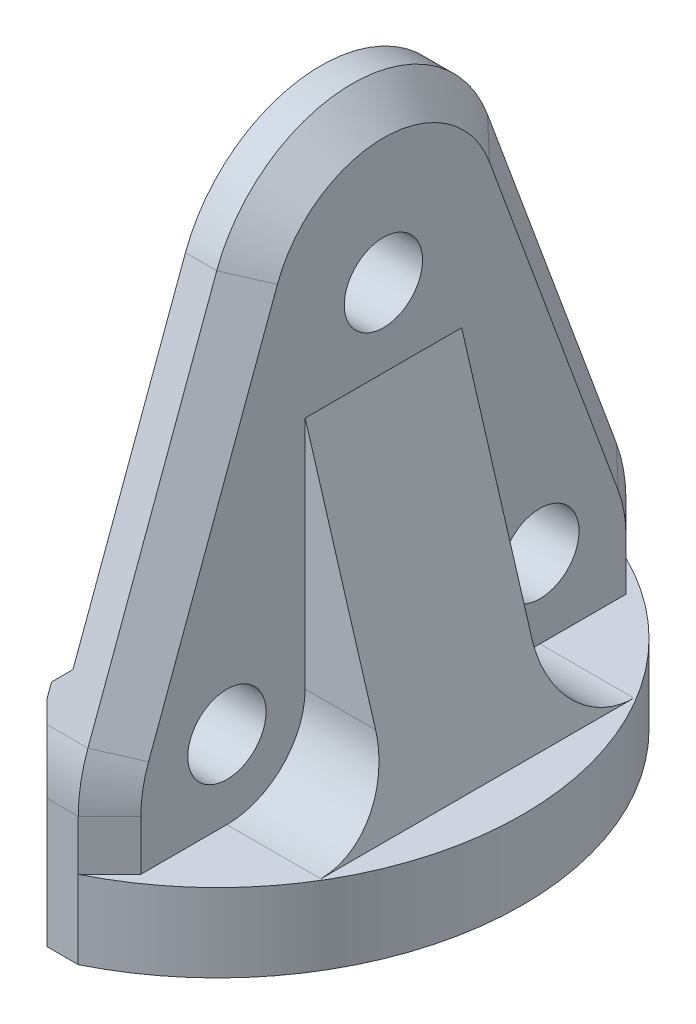
SolidWorks part; units mm, degrees
ref_plane "Front Plane" through (0, 0, 0) normal (0, 0, 1) x (1, 0, 0)
ref_plane "Top Plane" through (0, 0, 0) normal (0, 1, 0) x (1, 0, 0)
ref_plane "Right Plane" through (0, 0, 0) normal (1, 0, 0) x (0, 0, -1)
sketch "Sketch1" plane through (0, 0, 0) normal (1, 0, 0) x (0, 0, -1)
  line L0 (0, 0) -> (35, 0)
  line L1 (35, 0) -> (35, 8.213)
  line L2 (0, 0) -> (0, 8.21)
  line L3 (17.5, 1.5956) -> (17.5, 1.5986) construction
  line L4 (26.1505, 33.9741) -> (34.3813, 11.6759)
  line L5 (8.8494, 33.9737) -> (0.6186, 11.6724)
  arc A0 (0.6186, 11.6724) -> (0, 8.21) centre (10, 8.21) ccw
  arc A1 (17.5, 1.5986) -> (17.5013, 1.5971) centre (25, 8.213) ccw
  arc A2 (26.1505, 33.9741) -> (8.8494, 33.9737) centre (17.5, 30.781) ccw
  arc A5 (17.5, 1.5956) -> (17.5013, 1.5971) centre (10, 8.21) ccw
  arc A6 (35, 8.213) -> (34.3813, 11.6759) centre (25, 8.213) ccw
  dimension "D1" = 20
  dimension "D2" = 20
  dimension "D6" = 18.442
  dimension "D7" = 30.781
  dimension "D3" = 35
  dimension "D4" = 8.213
  dimension "D5" = 8.21
  dimension "D8" = 69.742
extrude "Boss-Extrude1" add sketch "Sketch1" along normal blind 2 contours L5 A0 L2 L0 L1 A6 L4 A2
sketch "Sketch2" plane through (2, 0, 0) normal (1, 0, 0) x (0, 0, -1)
  line L5 (8.8494, 33.9737) -> (0.6186, 11.6724)
  line L6 (0, 8.21) -> (0, 0)
  line L7 (0, 0) -> (35, 0)
  line L8 (35, 0) -> (35, 8.213)
  line L9 (34.3813, 11.6759) -> (26.1505, 33.9741)
  line L10 (8.8494, 33.9737) -> (0.6186, 11.6724)
  line L11 (0, 8.21) -> (0, 0)
  line L12 (0, 0) -> (35, 0)
  line L13 (35, 0) -> (35, 8.213)
  line L14 (34.3813, 11.6759) -> (26.1505, 33.9741)
  arc A3 (26.1505, 33.9741) -> (8.8494, 33.9737) centre (17.5, 30.781) ccw
  arc A4 (0.6186, 11.6724) -> (0, 8.21) centre (10, 8.21) ccw
  arc A5 (35, 8.213) -> (34.3813, 11.6759) centre (25, 8.213) ccw
  arc A6 (26.1505, 33.9741) -> (8.8494, 33.9737) centre (17.5, 30.781) ccw
  arc A7 (0.6186, 11.6724) -> (0, 8.21) centre (10, 8.21) ccw
  arc A8 (35, 8.213) -> (34.3813, 11.6759) centre (25, 8.213) ccw
  dimension "D1" = 0
extrude "Boss-Extrude2" add sketch "Sketch2" along normal blind 2 draft 45
sketch "Sketch4" plane through (0, 0, 0) normal (0, -1, 0) x (1, 0, 0)
  line L0 (0, 0) -> (2, 0)
  line L1 (0, 0) -> (0, -35)
  line L2 (0, -35) -> (2, -35)
  arc A0 (2, -35) -> (2, 0) centre (-6.6023, -17.5) ccw
  dimension "D1" = 39
extrude "Boss-Extrude3" add sketch "Sketch4" against normal blind 5
sketch "Sketch5" plane through (0, 0, 0) normal (-1, 0, 0) x (0, 0, 1)
  line L0 (0, 0) -> (0, 8.21) construction
  line L1 (-8.8494, 33.9737) -> (-0.6186, 11.6724) construction
  line L2 (-26.1505, 33.9741) -> (-34.3813, 11.6759) construction
  line L3 (-35, 0) -> (-35, 8.213) construction
  line L4 (0, 5.5) -> (0, 8.21)
  line L5 (-1.6621, 14.5) -> (-0.6186, 11.6724)
  line L6 (-33.3388, 14.5) -> (-34.3813, 11.6759)
  line L7 (-35, 5.5) -> (-35, 8.213)
  line L8 (-35, 5.5) -> (0, 5.5)
  line L9 (0, 0) -> (-35, 0) construction
  line L10 (-33.3388, 14.5) -> (-1.6621, 14.5)
  arc A0 (0, 8.21) -> (-0.6186, 11.6724) centre (-10, 8.21) ccw construction
  arc A1 (-34.3813, 11.6759) -> (-35, 8.213) centre (-25, 8.213) ccw construction
  arc A2 (0, 8.21) -> (-0.6186, 11.6724) centre (-10, 8.21) ccw
  arc A3 (-34.3813, 11.6759) -> (-35, 8.213) centre (-25, 8.213) ccw
  dimension "D1" = 5.5
  dimension "D2" = 9
extrude "Boss-Extrude4" add sketch "Sketch5" along normal blind 1
chamfer "Chamfer1" distance 1 angle 45 2 edges at (-1, 14.5, -17.5005) (-1, 5.5, -17.5)
chamfer "Chamfer2" distance 1 angle 45 2 edges at (-1, 7.355, 0) (-1, 7.3565, -35) tangent propagation no
sketch "Sketch6" plane through (-1, 0, 0) normal (-1, 0, 0) x (0, 0, 1)
  line L0 (-34, 12.7088) -> (-34, 6.5) construction
  line L1 (-1, 6.5) -> (-1, 12.706) construction
  line L2 (-34, 6.5) -> (-1, 6.5) construction
  circle A0 centre (-27.5, 10) radius 2.5
  circle A1 centre (-7.5, 10) radius 2.5
  dimension "D1" = 5
  dimension "D2" = 5
  dimension "D3" = 6.5
  dimension "D4" = 6.5
  dimension "D5" = 3.5
  dimension "D6" = 3.5
extrude "Cut-Extrude1" cut sketch "Sketch6" against normal through all
sketch "Sketch8" plane through (0, 0, 0) normal (-1, 0, 0) x (0, 0, 1)
  line L0 (0, 0) -> (-35, 0) construction
  circle A0 centre (-17.5, 29.999) radius 2.5
  arc A1 (-8.8494, 33.9737) -> (-26.1505, 33.9741) centre (-17.5, 30.781) ccw construction
  point P2 (0, 0)
  point P5 (-17.5, 0)
  dimension "D1" = 5
  dimension "D2" = 0.782
extrude "Cut-Extrude2" cut sketch "Sketch8" against normal through all
ref_plane "Plane1" through (0, 0, -22.5) normal (0, 0, -1) x (-1, 0, 0)
sketch "Sketch9" plane through (0, 0, -22.5) normal (0, 0, -1) x (-1, 0, 0)
  line L0 (-4, 5) -> (-4, 25)
  line L1 (-4, 10.9833) -> (-4, 33.2815) construction
  line L2 (-4, 25) -> (-10, 5)
  line L3 (-2, 5) -> (-12.8977, 5) construction
  line L4 (-10, 5) -> (-4, 5)
  dimension "D1" = 6
  dimension "D2" = 20
extrude "Boss-Extrude5" add sketch "Sketch9" against normal blind 10
fillet "Fillet1" radius 5 2 edges at (7, 5, -12.5) (7, 5, -22.5)
sketch "Sketch10" plane through (0, 0, 0) normal (-1, 0, 0) x (0, 0, 1)
  line L0 (-35, 5.5) -> (0, 5.5) construction
  line L1 (-20.5, 5) -> (-14.5, 5)
  line L2 (-20.5, 5) -> (-20.5, 2)
  line L3 (-20.5, 2) -> (-14.5, 2)
  line L4 (-14.5, 5) -> (-14.5, 2)
  line L5 (0, 0) -> (0, 5.5) construction
  point P8 (0, 2.75)
  dimension "D1" = 6
  dimension "D2" = 3
  dimension "D3" = 0.5
  dimension "D4" = 14.5
extrude "Cut-Extrude3" cut sketch "Sketch10" against normal blind 9
sketch "Sketch11" plane through (0, 0, 0) normal (0, -1, 0) x (1, 0, 0)
  line L0 (2, 0) -> (0, 0) construction
  line L1 (0, 0) -> (0, -35) construction
  circle A0 centre (5, -17.5) radius 1.7
  dimension "D1" = 3.4
  dimension "D2" = 17.5
  dimension "D3" = 5
extrude "Cut-Extrude4" cut sketch "Sketch11" against normal up to next
